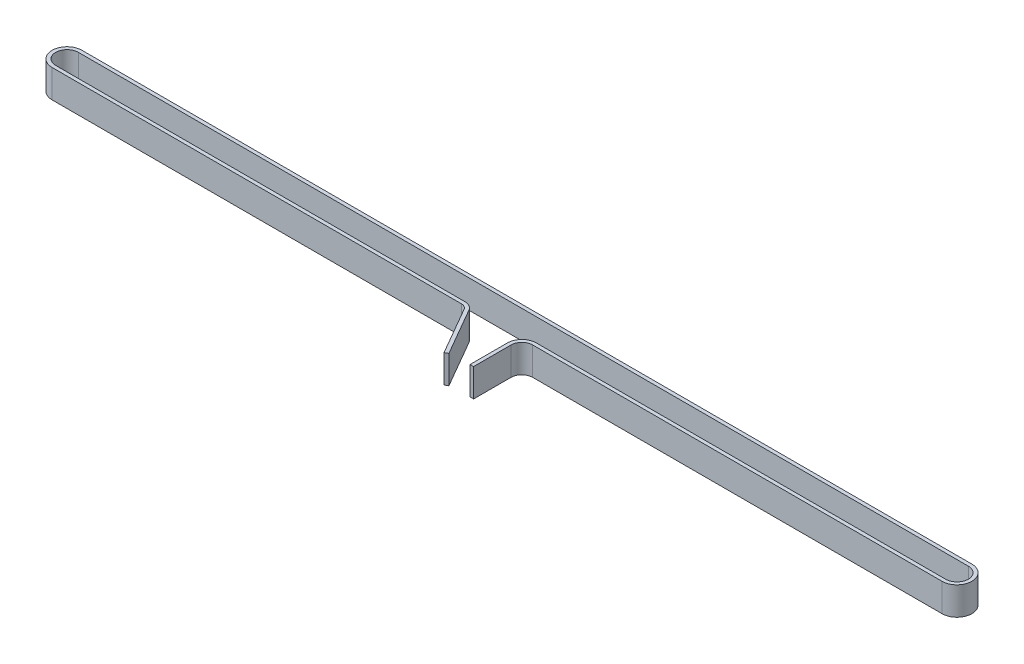
SolidWorks part; units mm, degrees
ref_plane "Front Plane" through (0, 0, 0) normal (0, 0, 1) x (1, 0, 0)
ref_plane "Top Plane" through (0, 0, 0) normal (0, 1, 0) x (1, 0, 0)
ref_plane "Right Plane" through (0, 0, 0) normal (1, 0, 0) x (0, 0, -1)
sketch "Sketch1" plane through (0, 0, 0) normal (0, 1, 0) x (1, 0, 0)
  line L0 (0, 6.365) -> (380, 6.365)
  line L1 (0, -6.365) -> (174.805, -6.365)
  line L2 (177.4031, -7.865) -> (189.1031, -28.13)
  line L3 (380, -6.365) -> (205.195, -6.365)
  line L4 (200.576, -10.984) -> (200.576, -26.984)
  arc A0 (0, 6.365) -> (0, -6.365) centre (0, 0) ccw
  arc A1 (380, -6.365) -> (380, 6.365) centre (380, 0) ccw
  arc A2 (205.195, -6.365) -> (200.576, -10.984) centre (205.195, -10.984) ccw
  arc A3 (174.805, -6.365) -> (177.4031, -7.865) centre (174.805, -9.365) cw
  point P12 (200.576, -6.365)
  point P16 (176.5371, -6.365)
  dimension "D1" = 380
  dimension "D2" = 12.73
  dimension "D4" = 4.619
  dimension "D6" = 3
  dimension "D3" = 16
  dimension "D5" = 120
  dimension "D7" = 23.4
  dimension "D8" = 30.39
extrude "Extrude-Thin1" add sketch "Sketch1" along normal blind 12 thin thin type one direction wall 1.52
